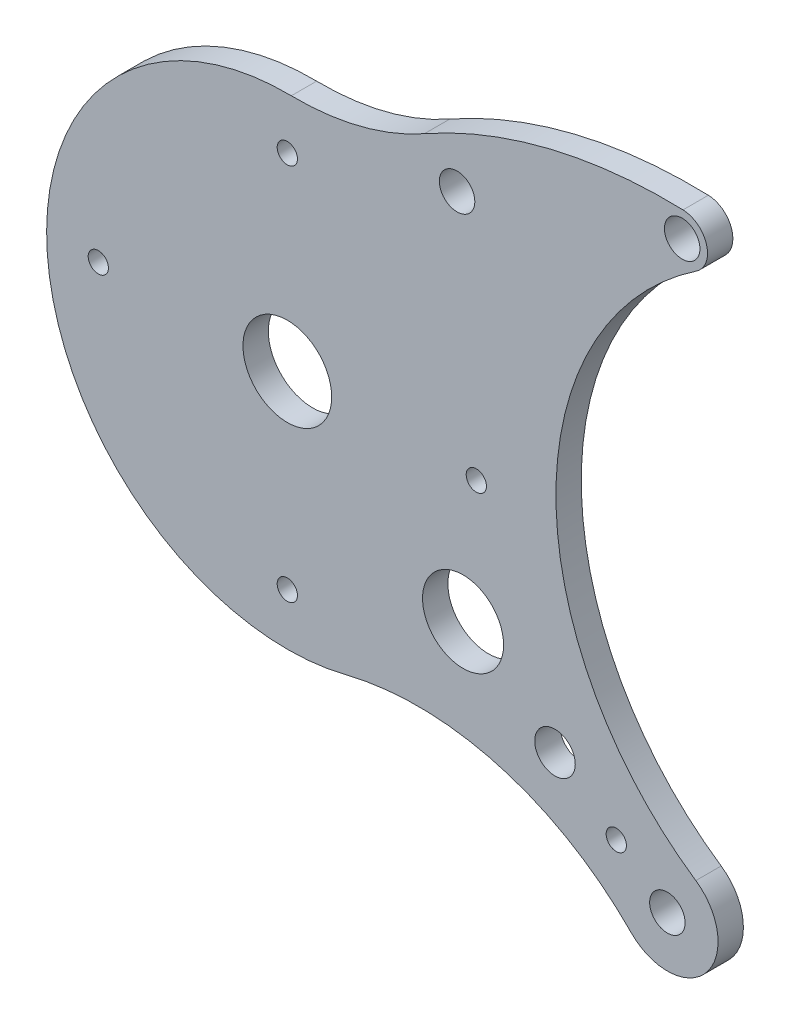
SolidWorks part; units mm, degrees
ref_plane "Front Plane" through (0, 0, 0) normal (0, 0, 1) x (1, 0, 0)
ref_plane "Top Plane" through (0, 0, 0) normal (0, 1, 0) x (1, 0, 0)
ref_plane "Right Plane" through (0, 0, 0) normal (1, 0, 0) x (0, 0, -1)
sketch "Sketch1" plane through (0, 0, 0) normal (0, 0, 1) x (1, 0, 0)
  arc A0 (1.5722, 94.987) -> (23.0489, -92.1615) centre (0, 0) ccw
  arc A1 (135.7114, -123.9942) -> (161.2252, -93.4472) centre (150, -110) ccw
  arc A2 (54.1221, 108.2997) -> (156.1718, 133.2815) centre (149.8103, -61.6578) cw
  arc A3 (161.4411, 114.9988) -> (156.1718, 133.2815) centre (155.8457, 123.2868) ccw
  arc A4 (54.1221, 108.2997) -> (1.5722, 94.987) centre (3.287, 198.5908) cw
  arc A5 (23.0489, -92.1615) -> (135.7114, -123.9942) centre (51.6099, -206.3628) cw
  arc A6 (161.2252, -93.4472) -> (161.4411, 114.9988) centre (231.8536, 10.7027) cw
  circle A7 centre (67, 95) radius 7
  circle A8 centre (155.8457, 123.2868) radius 7
  circle A9 centre (150, -110) radius 7
  circle A10 centre (0, 74.6) radius 4
  circle A11 centre (74.6, 0) radius 4
  circle A12 centre (0, -74.6) radius 4
  circle A13 centre (-74.6, 0) radius 4
  circle A14 centre (0, 0) radius 17.5
  point P3 (67, 95)
  point P4 (150, -110)
  point P5 (155.8457, 123.2868)
  dimension "D7" = 95
  dimension "D8" = 10
  dimension "D9" = 20
  dimension "D10" = 8
  dimension "D11" = 14
  dimension "D12" = 14
  dimension "D13" = 14
  dimension "D14" = 35
  dimension "D1" = 95
  dimension "D2" = 67
  dimension "D3" = 150
  dimension "D4" = 110
  dimension "D5" = 93.24
  dimension "D6" = 233.36
extrude "Boss-Extrude1" add sketch "Sketch1" along normal blind 10
sketch "Sketch4" plane through (0, 0, 10) normal (0, 0, 1) x (1, 0, 0)
  line L0 (0, 0) -> (150, -110) construction
  circle A0 centre (129.8399, -95.2159) radius 4
  circle A1 centre (105.6477, -77.475) radius 8
  circle A2 centre (69.3595, -50.8636) radius 16
  dimension "D4" = 8
  dimension "D5" = 16
  dimension "D6" = 32
  dimension "D1" = 30
  dimension "D2" = 45
  dimension "D3" = 25
extrude "Cut-Extrude1" cut sketch "Sketch4" against normal through all
